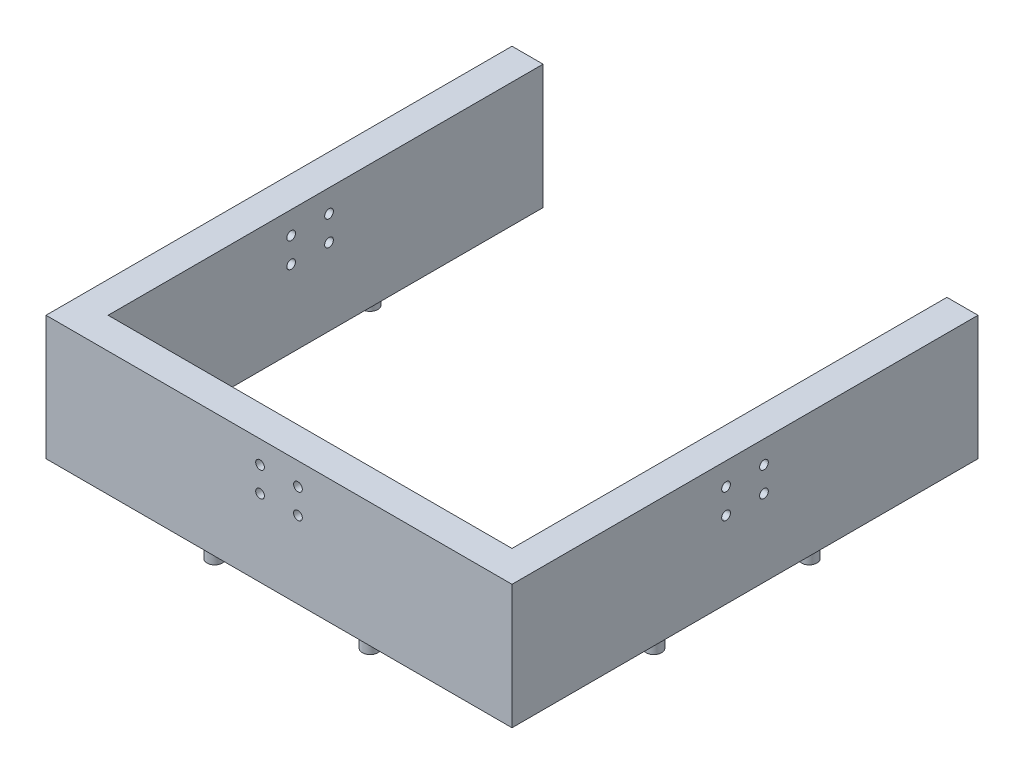
SolidWorks part; units mm, degrees
ref_plane "Front" through (0, 0, 0) normal (0, 0, 1) x (1, 0, 0)
ref_plane "Top" through (0, 0, 0) normal (0, 1, 0) x (1, 0, 0)
ref_plane "Right" through (0, 0, 0) normal (1, 0, 0) x (0, 0, -1)
sketch "Sketch1" plane through (0, 0, 0) normal (0, 1, 0) x (1, 0, 0)
  line L1 (-75, -75) -> (75, -75)
  line L2 (-75, -75) -> (-75, 75)
  line L3 (-75, 75) -> (75, 75)
  line L4 (75, -75) -> (75, 75)
  line L5 (-75, -75) -> (75, 75) construction
  line L6 (-75, 75) -> (75, -75) construction
  point P0 (0, 0)
  dimension "D1" = 150
  dimension "D2" = 150
extrude "Boss-Extrude1" add sketch "Sketch1" against normal blind 40
sketch "Sketch2" plane through (0, 0, 0) normal (0, 1, 0) x (1, 0, 0)
  line L1 (-65, -65) -> (65, -65)
  line L2 (-65, -65) -> (-65, 65)
  line L3 (-65, 65) -> (65, 65)
  line L4 (65, -65) -> (65, 65)
  line L5 (-65, -65) -> (65, 65) construction
  line L6 (-65, 65) -> (65, -65) construction
  point P0 (0, 0)
  dimension "D1" = 130
  dimension "D2" = 130
extrude "Cut-Extrude1" cut sketch "Sketch2" against normal blind 54
sketch "Sketch4" plane through (0, 0, -65) normal (0, 0, 1) x (1, 0, 0)
  line L3 (65, 0) -> (-65, 0) construction
  line L4 (-3.5, -17.47) -> (1.5, -17.47)
  line L5 (-3.5, -17.47) -> (-3.5, 0)
  line L6 (-3.5, 0) -> (1.5, 0)
  line L7 (1.5, -17.47) -> (1.5, 0)
  line L8 (-3.5, -17.47) -> (1.5, 0) construction
  line L9 (-3.5, 0) -> (1.5, -17.47) construction
  point P6 (-1, -8.735)
  dimension "D1" = 5
ref_axis "Axis1" through (0, 0, 0) along (0, -1, 0)
sketch "Sketch6" plane through (0, -40, 0) normal (0, -1, 0) x (1, 0, 0)
  line L0 (75, -75) -> (-75, -75) construction
  line L1 (-75, 75) -> (75, 75) construction
  circle A0 centre (-70.6782, -25) radius 2.5
  circle A1 centre (-70.6782, 25) radius 2.5
  circle A2 centre (25, 70.6782) radius 2.5
  circle A3 centre (-25, 70.6782) radius 2.5
  circle A4 centre (70.6782, -25) radius 2.5
  circle A5 centre (70.6782, 25) radius 2.5
  circle A6 centre (-25, -70.6782) radius 2.5
  circle A7 centre (25, -70.6782) radius 2.5
  dimension "D1" = 5
  dimension "D3" = 5
  dimension "D2" = 50
  dimension "D4" = 50
  dimension "D5" = 4
extrude "Boss-Extrude5" add sketch "Sketch6" along normal blind 5
sketch "Sketch9" plane through (-75, 0, 0) normal (-1, 0, 0) x (0, 0, 1)
  line L0 (-75, 0) -> (75, 0) construction
  line L1 (0, 0) -> (7.5, 0)
  line L7 (0, 0) -> (-7.5, 0)
  circle A0 centre (-6.1, -7.25) radius 1.4
  circle A1 centre (6.1, -7.25) radius 1.4
  circle A2 centre (6.1, -15.25) radius 1.4
  circle A3 centre (-6.1, -15.25) radius 1.4
  dimension "D4" = 2.8
  dimension "D2" = 7.5
  dimension "D3" = 7.5
  dimension "D5" = 7.25
extrude "Cut-Extrude4" cut sketch "Sketch9" against normal blind 10 contours A0 | A1 | A2 | A3 region at (-75, -7.25, -6.1)
pattern_circular "CirPattern1" count 3 every 90 about axis through (0, 0, 0) along (0, -1, 0) of "Cut-Extrude4" reverse direction yes
sketch "Sketch10" plane through (0, 0, 0) normal (0, 1, 0) x (1, 0, 0)
  line L0 (-65, 65) -> (65, 65)
  line L1 (-65, 65) -> (-65, 161.3983)
  line L2 (65, 65) -> (65, 161.3983)
  line L3 (-65, 161.3983) -> (65, 161.3983)
extrude "Cut-Extrude6" cut sketch "Sketch10" against normal through all
